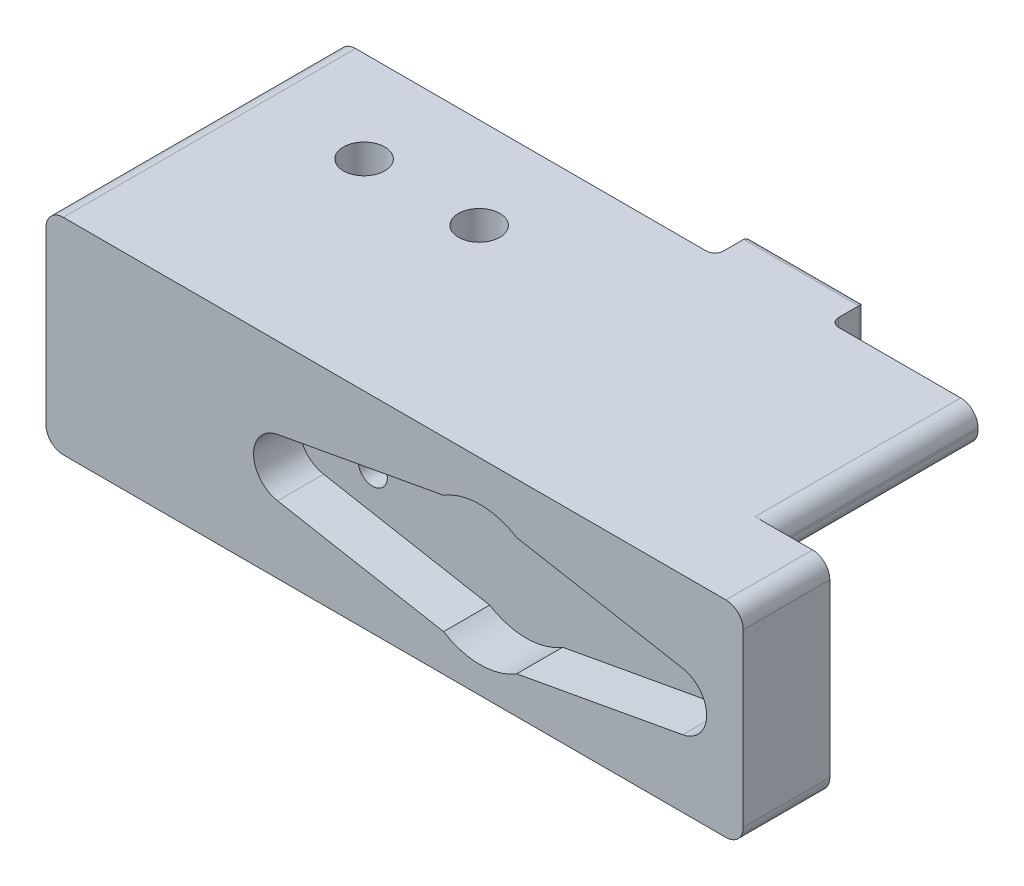
SolidWorks part; units mm, degrees
ref_plane "Front Plane" through (0, 0, 0) normal (0, 0, 1) x (1, 0, 0)
ref_plane "Top Plane" through (0, 0, 0) normal (0, 1, 0) x (1, 0, 0)
ref_plane "Right Plane" through (0, 0, 0) normal (1, 0, 0) x (0, 0, -1)
sketch "Sketch1" plane through (0, 0, 0) normal (0, 0, 1) x (1, 0, 0)
  line L1 (-37.719, -6.35) -> (37.719, -6.35)
  line L2 (-37.719, -6.35) -> (-37.719, 6.35)
  line L3 (-37.719, 6.35) -> (37.719, 6.35)
  line L4 (37.719, -6.35) -> (37.719, 6.35)
  line L5 (0, 6.35) -> (0, -6.35) construction
  line L6 (-37.719, 0) -> (37.719, 0) construction
  point P0 (0, 0)
  dimension "D1" = 75.438
  dimension "D2" = 12.7
extrude "Boss-Extrude1" add sketch "Sketch1" along normal blind 6.35
sketch "Sketch2" plane through (0, 0, 6.35) normal (0, 0, 1) x (1, 0, 0)
  line L1 (0, 0) -> (3.175, 5.1294) construction
  line L2 (0, -1000) -> (0, 49000) construction
  line L3 (3.175, 5.1294) -> (17.6007, 2.4988)
  line L4 (-1000, 0) -> (49000, 0) construction
  line L5 (3.175, -5.1294) -> (17.6007, -2.4988)
  line L6 (-3.175, -5.1294) -> (-17.6007, -2.4988)
  line L7 (-3.175, 5.1294) -> (-17.6007, 2.4988)
  arc A0 (-3.175, -5.1294) -> (3.175, -5.1294) centre (0, 0) ccw
  arc A1 (17.6007, -2.4988) -> (17.6007, 2.4988) centre (17.145, 0) ccw
  arc A2 (-17.6007, -2.4988) -> (-17.6007, 2.4988) centre (-17.145, 0) cw
  arc A3 (3.175, 5.1294) -> (-3.175, 5.1294) centre (0, 0) ccw
  dimension "D1" = 12.065
  dimension "D2" = 5.08
  dimension "D3" = 17.145
  dimension "D4" = 3.175
extrude "Cut-Extrude1" cut sketch "Sketch2" against normal blind 4
sketch "Sketch3" plane through (0, 0, 0) normal (0, 1, 0) x (1, 0, 0)
  line L0 (-34.544, 3.175) -> (34.544, 3.175)
  line L1 (-37.719, 0) -> (37.719, 0)
  line L2 (-37.719, 0) -> (-37.719, 19.05)
  line L3 (-37.719, 19.05) -> (37.719, 19.05)
  line L4 (37.719, 0) -> (37.719, 19.05)
  line L5 (34.544, 3.175) -> (34.544, 15.875)
  line L6 (-34.544, 15.875) -> (34.544, 15.875)
  line L7 (-34.544, 3.175) -> (-34.544, 15.875)
  dimension "D2" = 19.05
  dimension "D1" = 3.175
extrude "Boss-Extrude2" add sketch "Sketch3" along normal up to surface and the other way up to surface up to face at (0, 6.35, 3.175) other way up to face at (0, -6.35, 3.175)
sketch "Sketch4" plane through (0, 6.35, 0) normal (0, 1, 0) x (1, 0, 0)
  line L0 (-37.719, -6.35) -> (-37.719, 19.05) construction
  line L1 (-37.719, -6.35) -> (37.719, -6.35)
  line L2 (-37.719, -6.35) -> (-37.719, 19.05)
  line L3 (-37.719, 19.05) -> (37.719, 19.05)
  line L4 (37.719, -6.35) -> (37.719, 19.05)
extrude "Boss-Extrude4" add sketch "Sketch4" along normal blind 3.175
sketch "Sketch7" plane through (0, 0, 6.35) normal (0, 0, 1) x (1, 0, 0)
  line L0 (-37.719, 9.525) -> (37.719, 9.525) construction
  line L1 (37.719, -6.35) -> (22.86, -6.35)
  line L2 (37.719, -6.35) -> (37.719, 9.525)
  line L3 (37.719, 9.525) -> (22.86, 9.525)
  line L4 (22.86, -6.35) -> (22.86, 9.525)
  arc A0 (17.6007, -2.4988) -> (17.6007, 2.4988) centre (17.145, 0) ccw construction
  point P10 (19.685, 0)
  dimension "D1" = 3.175
extrude "Cut-Extrude3" cut sketch "Sketch7" against normal through all
sketch "Sketch8" plane through (22.86, 0, 0) normal (1, 0, 0) x (0, 0, -1)
  line L1 (15.875, -6.35) -> (19.05, -6.35)
  line L2 (15.875, -6.35) -> (15.875, 9.525)
  line L3 (15.875, 9.525) -> (19.05, 9.525)
  line L4 (19.05, -6.35) -> (19.05, 9.525)
extrude "Cut-Extrude4" cut sketch "Sketch8" against normal through all
sketch "Sketch9" plane through (0, 0, -15.875) normal (0, 0, -1) x (-1, 0, 0)
  line L6 (34.544, 6.35) -> (34.544, -6.35)
  line L7 (34.544, -6.35) -> (37.719, -6.35)
  line L8 (37.719, -6.35) -> (37.719, 9.525)
  line L9 (37.719, 9.525) -> (-22.86, 9.525)
  line L10 (-22.86, 9.525) -> (-22.86, 6.35)
  line L11 (-22.86, 6.35) -> (34.544, 6.35)
  line L12 (34.544, 6.35) -> (34.544, -6.35)
  line L13 (34.544, -6.35) -> (37.719, -6.35)
  line L14 (37.719, -6.35) -> (37.719, 9.525)
  line L15 (37.719, 9.525) -> (-22.86, 9.525)
  line L16 (-22.86, 9.525) -> (-22.86, 6.35)
  line L17 (-22.86, 6.35) -> (34.544, 6.35)
  dimension "D1" = 0
extrude "Boss-Extrude5" add sketch "Sketch9" along normal blind 3.175
sketch "Sketch10" plane through (0, 6.35, 0) normal (0, -1, 0) x (1, 0, 0)
  line L0 (-1034.544, -11.1125) -> (48965.456, -11.1125) construction
  line L1 (-34.544, -3.175) -> (-34.544, -19.05) construction
  line L2 (-1042.3688, -14.9275) -> (48957.6312, -14.9275) construction
  circle A0 centre (-27.544, -11.1125) radius 1.8
  circle A1 centre (-17.544, -11.1125) radius 1.8
  point P9 (-34.544, -11.1125)
  dimension "D3" = 3.6
  dimension "D4" = 3.6
  dimension "D1" = 10
  dimension "D2" = 7
sketch "Sketch11" plane through (0, 0, -3.175) normal (0, 0, -1) x (-1, 0, 0)
  line L1 (-22.86, 6.35) -> (34.544, 6.35)
  line L2 (-22.86, 6.35) -> (-22.86, -6.35)
  line L3 (-22.86, -6.35) -> (34.544, -6.35)
  line L4 (34.544, 6.35) -> (34.544, -6.35)
extrude "Cut-Extrude5" cut sketch "Sketch11" against normal blind 2
sketch "Sketch12" plane through (0, 0, 2.35) normal (0, 0, 1) x (1, 0, 0)
  line L0 (0, -1000) -> (0, 49000) construction
  circle A0 centre (13.335, 0) radius 1.27
  circle A1 centre (-13.335, 0) radius 1.27
  dimension "D1" = 2.54
  dimension "D2" = 13.335
extrude "Cut-Extrude6" cut sketch "Sketch12" against normal through all
extrude "Cut-Extrude7" cut sketch "Sketch10" against normal through all
sketch "Sketch13" plane through (22.86, 0, 0) normal (1, 0, 0) x (0, 0, -1)
  line L1 (1.175, 6.35) -> (19.05, 6.35)
  line L2 (1.175, 6.35) -> (1.175, 9.525)
  line L3 (1.175, 9.525) -> (19.05, 9.525)
  line L4 (19.05, 6.35) -> (19.05, 9.525)
extrude "Cut-Extrude8" cut sketch "Sketch13" against normal blind 5
sketch "Sketch14" plane through (0, 0, -19.05) normal (0, 0, -1) x (-1, 0, 0)
  line L5 (0, -1000) -> (0, 49000) construction
  line L6 (37.719, 9.525) -> (-17.86, 9.525) construction
  line L7 (-5, -5.1301) -> (5, -5.1301)
  line L8 (-5, -5.1301) -> (-5, 9.525)
  line L9 (-5, 9.525) -> (5, 9.525)
  line L10 (5, -5.1301) -> (5, 9.525)
  line L11 (0, 9.525) -> (0, -5.1301) construction
  line L12 (-5, 2.1975) -> (5, 2.1975) construction
  point P1 (0, 2.1975)
  dimension "D1" = 10
extrude "Boss-Extrude6" add sketch "Sketch14" along normal blind 3
sketch "Sketch15" plane through (0, 0, -22.05) normal (0, 0, -1) x (-1, 0, 0)
  circle A0 centre (0, 0) radius 2.1
  dimension "D1" = 4.2
extrude "Cut-Extrude9" cut sketch "Sketch15" against normal blind 2
sketch "Sketch16" plane through (0, -6.35, 0) normal (0, -1, 0) x (1, 0, 0)
  line L6 (-34.544, -19.05) -> (-34.544, -1.175)
  line L7 (-34.544, -1.175) -> (22.86, -1.175)
  line L8 (22.86, -1.175) -> (22.86, 6.35)
  line L9 (22.86, 6.35) -> (-37.719, 6.35)
  line L10 (-37.719, 6.35) -> (-37.719, -19.05)
  line L11 (-37.719, -19.05) -> (-34.544, -19.05)
  line L12 (-34.544, -19.05) -> (-34.544, -1.175)
  line L13 (-34.544, -1.175) -> (22.86, -1.175)
  line L14 (22.86, -1.175) -> (22.86, 6.35)
  line L15 (22.86, 6.35) -> (-37.719, 6.35)
  line L16 (-37.719, 6.35) -> (-37.719, -19.05)
  line L17 (-37.719, -19.05) -> (-34.544, -19.05)
  dimension "D1" = 0
extrude "Boss-Extrude7" add sketch "Sketch16" along normal blind 2
fillet "Fillet3" radius 0.5 6 edges at (-5, -5.1301, -20.55) (5, -5.1301, -20.55) (5, 2.1975, -22.05) (-5, 2.1975, -22.05) (0, -5.1301, -22.05) (0, 9.525, -22.05)
fillet "Fillet4" radius 0.75 1 edges at (5, 7.9375, -19.05) type face fillet first side face at (11.43, 7.9375, -19.05) second side face at (5, 3.228, -20.05)
fillet "Fillet5" radius 0.75 1 edges at (-5, 7.9375, -19.05) type face fillet first side face at (-5, 3.228, -20.05) second side face at (-25.7543, 2.5083, -19.05)
fillet "Fillet6" radius 0.75 1 edges at (0, 6.35, -19.05) type face fillet first side face at (-3.3368, 6.35, -15.5939) second side face at (0, -1.1712, -19.05)
fillet "Fillet2" radius 1.5 8 edges at (-37.719, 9.525, -6.35) (-34.544, 6.35, -10.1125) (22.86, 9.525, 2.5875) (17.86, 9.525, -10.1125) (17.86, 6.35, -10.1125) (-37.719, -8.35, -6.35) (22.86, -8.35, 2.5875) (-34.544, -8.35, -10.1125)
